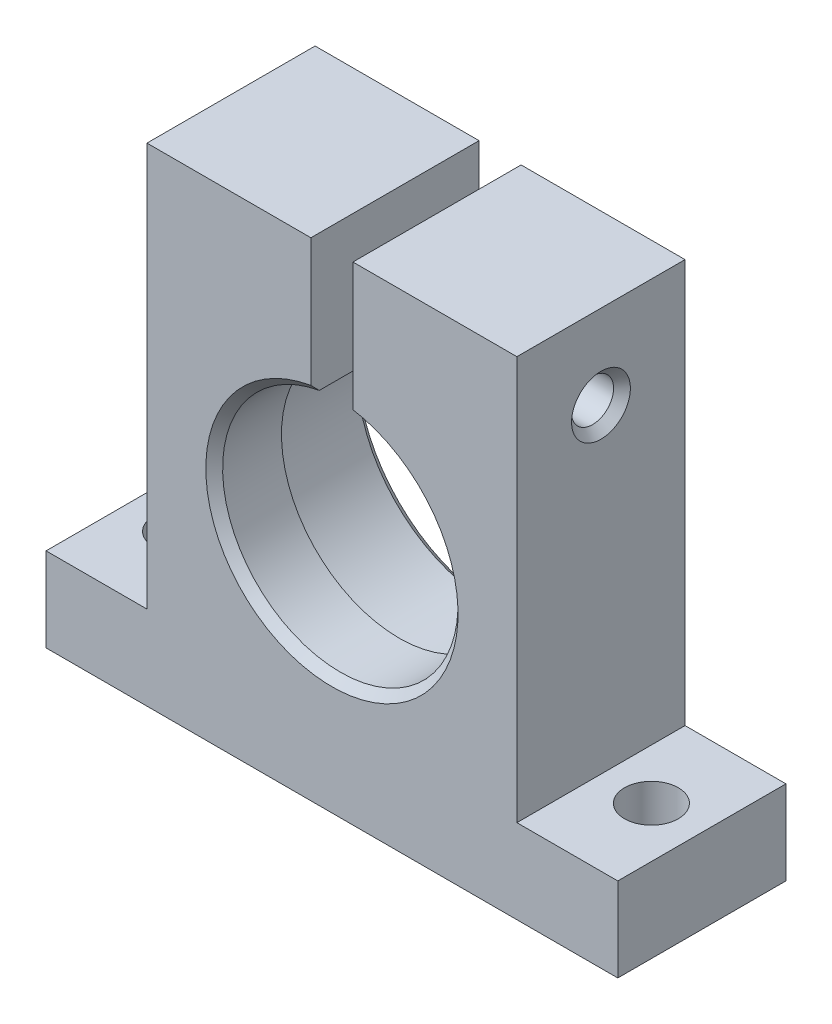
SolidWorks part; units mm, degrees
material "AISI 1045 Steel, cold drawn"
ref_plane "Front Plane" through (0, 0, 0) normal (0, 0, 1) x (1, 0, 0)
ref_plane "Top Plane" through (0, 0, 0) normal (0, 1, 0) x (1, 0, 0)
ref_plane "Right Plane" through (0, 0, 0) normal (1, 0, 0) x (0, 0, -1)
sketch "Sketch1" plane through (0, 0, 0) normal (0, 0, 1) x (1, 0, 0)
  line L1 (11, -14) -> (-11, -14)
  line L2 (11, -14) -> (11, 15)
  line L3 (11, 15) -> (-11, 15)
  line L4 (-11, -14) -> (-11, 15)
  line L5 (11, -14) -> (-11, 15) construction
  line L6 (11, 15) -> (-11, -14) construction
  circle A0 centre (0, 0) radius 8 construction
  point P3 (0, 0.5)
  dimension "D1" = 16
  dimension "D2" = 29
  dimension "D3" = 15
  dimension "D4" = 22
extrude "Boss-Extrude1" add sketch "Sketch1" along normal mid plane 10
sketch "Sketch3" plane through (0, -14, 0) normal (0, -1, 0) x (1, 0, 0)
  line L0 (-11, 5) -> (11, 5) construction
  line L1 (17, -5) -> (-17, -5)
  line L2 (17, -5) -> (17, 5)
  line L3 (17, 5) -> (-17, 5)
  line L4 (-17, -5) -> (-17, 5)
  line L5 (17, -5) -> (-17, 5) construction
  line L6 (17, 5) -> (-17, -5) construction
  point P0 (0, 0)
  dimension "D1" = 34
extrude "Boss-Extrude2" add sketch "Sketch3" against normal blind 5
hole_wizard "Ø16.0 (16) Diameter Hole1" positions "Sketch4" profile "Sketch5" hole size "Ø16.0" standard "ANSI Metric"
sketch "Sketch4" plane through (0, 0, -5) normal (0, 0, -1) x (-1, 0, 0)
  point P0 (0, 0)
sketch "Sketch5" plane through (0, 0, -5) normal (1, 0, 0) x (0, 1, 0)
  line L0 (0, 0) -> (0, 6)
  line L1 (0, 6) -> (8, 6)
  line L2 (8, 6) -> (8, 0)
  line L5 (8, 0) -> (0, 0)
  line L10 (0, 6) -> (-8, 6) construction
  line L11 (0, -6.35) -> (0, 107.95) construction
  dimension "Hole Dia." = 16
  dimension "Hole Depth" = 6
  dimension "Drill Angle" = 180
hole_wizard "Ø14.0 (14) Diameter Hole1" positions "Sketch13" profile "Sketch14" hole size "Ø14.0" standard "ANSI Metric" end condition through all
sketch "Sketch13" plane through (0, 0, 1) normal (0, 0, -1) x (-1, 0, 0)
  point P0 (0, 0)
sketch "Sketch14" plane through (0, 0, 1) normal (1, 0, 0) x (0, 1, 0)
  line L0 (0, 0) -> (0, 4)
  line L1 (0, 4) -> (7, 4)
  line L2 (7, 4) -> (7, 0)
  line L5 (7, 0) -> (0, 0)
  line L11 (0, -6.35) -> (0, 107.95) construction
  dimension "Thru Hole Dia." = 14
  dimension "Thru Hole Depth" = 4
hole_wizard "M3 Clearance Hole1" positions "Sketch6" profile "Sketch7" hole size "M3" standard "ANSI Metric" end condition through all
sketch "Sketch6" plane through (0, -9, 0) normal (0, 1, 0) x (1, 0, 0)
  line L0 (-17, -5) -> (-11, 5) construction
  line L2 (17, -5) -> (11, 5) construction
  point P0 (-14, 0)
  point P2 (14, 0)
sketch "Sketch7" plane through (-14, -9, 0) normal (1, 0, 0) x (0, 0, 1)
  line L0 (0, 0) -> (0, 5)
  line L1 (0, 5) -> (1.6, 5)
  line L2 (1.6, 5) -> (1.6, 0)
  line L5 (1.6, 0) -> (0, 0)
  line L11 (0, -6.35) -> (0, 107.95) construction
  dimension "Thru Hole Dia." = 3.2
  dimension "Thru Hole Depth" = 5
sketch "Sketch12" plane through (0, 0, 5) normal (0, 0, 1) x (1, 0, 0)
  line L0 (11, 15) -> (-11, 15) construction
  line L1 (1.25, 6.8875) -> (-1.25, 6.8875)
  line L2 (1.25, 6.8875) -> (1.25, 15)
  line L3 (1.25, 15) -> (-1.25, 15)
  line L4 (-1.25, 6.8875) -> (-1.25, 15)
  line L5 (1.25, 6.8875) -> (-1.25, 15) construction
  line L6 (1.25, 15) -> (-1.25, 6.8875) construction
  circle A1 centre (0, 0) radius 7 construction
  point P0 (0, 10.9437)
  dimension "D1" = 2.5
extrude "Cut-Extrude1" cut sketch "Sketch12" against normal through all
hole_wizard "M3x0.5 Tapped Hole1" positions "Sketch8" profile "Sketch9" tap size "M3x0.5" standard "ANSI Metric" end condition up to next
sketch "Sketch8" plane through (-11, 0, 0) normal (-1, 0, 0) x (0, 0, 1)
  line L0 (5, 15) -> (-5, 15) construction
  point P0 (0, 10)
  dimension "D1" = 5
sketch "Sketch9" plane through (-11, 10, 0) normal (0, 1, 0) x (0, 0, 1)
  line L0 (0, 0) -> (0, 9.75)
  line L1 (0, 9.75) -> (1.25, 9.75)
  line L2 (1.25, 9.75) -> (1.25, 0)
  line L5 (1.25, 0) -> (0, 0)
  line L11 (0, -6.35) -> (0, 107.95) construction
  dimension "Thru Tap Drill Dia." = 2.5
  dimension "Thru Tap Drill Depth" = 9.75
cosmetic thread "Hole Thread1" parameters "D2"=3
hole_wizard "CBORE for M3 SHCS1" positions "Sketch10" profile "Sketch11" counterbore size "M3" standard "ANSI Metric" end condition up to next
sketch "Sketch10" plane through (11, 0, 0) normal (1, 0, 0) x (0, 0, -1)
  point P0 (0, 10)
sketch "Sketch11" plane through (11, 10, 0) normal (0, 1, 0) x (0, 0, -1)
  line L0 (0, 0) -> (0, 9.75)
  line L1 (0, 9.75) -> (1.6, 9.75)
  line L3 (1.6, 9.75) -> (1.6, 3)
  line L4 (1.6, 3) -> (3.25, 3)
  line L5 (3.25, 3) -> (3.25, 0)
  line L7 (3.25, 0) -> (0, 0)
  line L11 (0, -6.35) -> (0, 107.95) construction
  dimension "Thru Hole Dia." = 3.2
  dimension "Thru Hole Depth" = 9.75
  dimension "C'Bore Dia." = 6.5
  dimension "C'Bore Depth" = 3
chamfer "Chamfer1" distance 0.5 angle 45 3 edges at (0, -8, -5) (0, -7, 5) (-11, 10, 1.25)
mirror "Mirror1" about plane through (-17, -9, -5) normal (-1, 0, 0) of bodies 106
cosmetic thread "Hole Thread2" parameters "D2"=3
delete or keep bodies "Body-Delete/Keep 1" type delete bodies bodies 106
